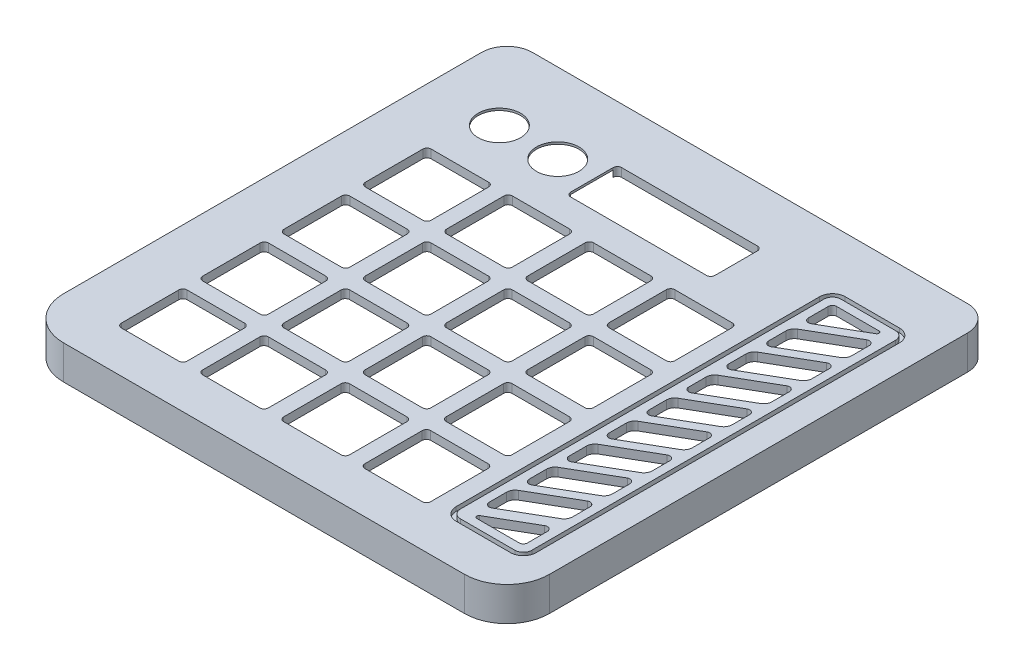
SolidWorks part; units mm, degrees
ref_plane "Plan de face" through (0, 0, 0) normal (0, 0, 1) x (1, 0, 0)
ref_plane "Plan de dessus" through (0, 0, 0) normal (0, 1, 0) x (1, 0, 0)
ref_plane "Plan de droite" through (0, 0, 0) normal (1, 0, 0) x (0, 0, -1)
sketch "Esquisse2" plane through (0, 0, 0) normal (0, 1, 0) x (1, 0, 0)
  line L1 (8, 0) -> (102.5, 0)
  line L2 (0, 8) -> (0, 106.5)
  line L3 (4, 110.5) -> (106.5, 110.5)
  line L4 (110.5, 8) -> (110.5, 106.5)
  line L5 (8, -2) -> (102.5, -2)
  line L6 (-2, 8) -> (-2, 106.5)
  line L7 (4, 112.5) -> (106.5, 112.5)
  line L8 (112.5, 8) -> (112.5, 106.5)
  arc A0 (0, 106.5) -> (4, 110.5) centre (4, 106.5) cw
  arc A1 (106.5, 110.5) -> (110.5, 106.5) centre (106.5, 106.5) cw
  arc A2 (102.5, 0) -> (110.5, 8) centre (102.5, 8) ccw
  arc A3 (8, 0) -> (0, 8) centre (8, 8) cw
  arc A4 (-2, 106.5) -> (4, 112.5) centre (4, 106.5) cw
  arc A5 (112.5, 106.5) -> (106.5, 112.5) centre (106.5, 106.5) ccw
  arc A6 (102.5, -2) -> (112.5, 8) centre (102.5, 8) ccw
  arc A7 (8, -2) -> (-2, 8) centre (8, 8) cw
  point P7 (0, 110.5)
  point P12 (110.5, 0)
  point P15 (0, 0)
  dimension "D3" = 4
  dimension "D4" = 8
  dimension "D9" = 6
  dimension "D10" = 6
  dimension "D11" = 10
  dimension "D1" = 110.5
  dimension "D2" = 110.5
  dimension "D5" = 2
  dimension "D6" = 2
  dimension "D7" = 2
  dimension "D8" = 2
extrude "Boss.-Extru.1" add sketch "Esquisse2" along normal blind 6
sketch "Esquisse3" plane through (0, 6, 0) normal (0, 1, 0) x (1, 0, 0)
  line L0 (-2, 106.5) -> (-2, 112.5) construction
  line L1 (4, 112.5) -> (-2, 112.5) construction
  line L2 (102.5, -2) -> (112.5, -2) construction
  line L3 (4, 112.5) -> (106.5, 112.5)
  line L4 (-2, 106.5) -> (-2, 8)
  line L5 (8, -2) -> (102.5, -2)
  line L6 (112.5, 106.5) -> (112.5, 8)
  line L7 (112.5, 8) -> (112.5, -2) construction
  arc A0 (106.5, 112.5) -> (112.5, 106.5) centre (106.5, 106.5) cw
  arc A1 (4, 112.5) -> (-2, 106.5) centre (4, 106.5) ccw
  arc A2 (102.5, -2) -> (112.5, 8) centre (102.5, 8) ccw
  arc A3 (-2, 8) -> (8, -2) centre (8, 8) ccw
  dimension "D1" = 6
  dimension "D2" = 10
extrude "Boss.-Extru.2" add sketch "Esquisse3" along normal blind 2
sketch "Esquisse5" plane through (0, 8, 0) normal (0, 1, 0) x (1, 0, 0)
  line L0 (112.5, 8) -> (112.5, 106.5) construction
  line L5 (-2, 106.5) -> (-2, 8) construction
  line L6 (38, 87.5) -> (70, 87.5)
  line L8 (11.8, 80.849) -> (25.3, 80.849)
  line L9 (10.8, 79.849) -> (10.8, 66.349)
  line L10 (11.8, 65.349) -> (25.3, 65.349)
  line L11 (26.3, 79.849) -> (26.3, 66.349)
  line L75 (29.9262, 79.849) -> (29.9262, 66.349)
  line L76 (30.9262, 80.849) -> (44.4262, 80.849)
  line L77 (45.4262, 79.849) -> (45.4262, 66.349)
  line L78 (30.9262, 65.349) -> (44.4262, 65.349)
  line L79 (49.0524, 79.849) -> (49.0524, 66.349)
  line L80 (50.0524, 80.849) -> (63.5524, 80.849)
  line L81 (64.5524, 79.849) -> (64.5524, 66.349)
  line L82 (50.0524, 65.349) -> (63.5524, 65.349)
  line L83 (68.1786, 79.849) -> (68.1786, 66.349)
  line L84 (69.1786, 80.849) -> (82.6786, 80.849)
  line L85 (83.6786, 79.849) -> (83.6786, 66.349)
  line L86 (69.1786, 65.349) -> (82.6786, 65.349)
  line L87 (29.9262, 60.6815) -> (29.9262, 47.1815)
  line L88 (30.9262, 61.6815) -> (44.4262, 61.6815)
  line L89 (45.4262, 60.6815) -> (45.4262, 47.1815)
  line L90 (30.9262, 46.1815) -> (44.4262, 46.1815)
  line L91 (49.0524, 60.6815) -> (49.0524, 47.1815)
  line L92 (50.0524, 61.6815) -> (63.5524, 61.6815)
  line L93 (64.5524, 60.6815) -> (64.5524, 47.1815)
  line L94 (50.0524, 46.1815) -> (63.5524, 46.1815)
  line L95 (68.1786, 60.6815) -> (68.1786, 47.1815)
  line L96 (69.1786, 61.6815) -> (82.6786, 61.6815)
  line L97 (83.6786, 60.6815) -> (83.6786, 47.1815)
  line L98 (69.1786, 46.1815) -> (82.6786, 46.1815)
  line L99 (29.9262, 41.514) -> (29.9262, 28.014)
  line L100 (30.9262, 42.514) -> (44.4262, 42.514)
  line L101 (45.4262, 41.514) -> (45.4262, 28.014)
  line L102 (30.9262, 27.014) -> (44.4262, 27.014)
  line L103 (49.0524, 41.514) -> (49.0524, 28.014)
  line L104 (50.0524, 42.514) -> (63.5524, 42.514)
  line L105 (64.5524, 41.514) -> (64.5524, 28.014)
  line L106 (50.0524, 27.014) -> (63.5524, 27.014)
  line L107 (68.1786, 41.514) -> (68.1786, 28.014)
  line L108 (69.1786, 42.514) -> (82.6786, 42.514)
  line L109 (83.6786, 41.514) -> (83.6786, 28.014)
  line L110 (69.1786, 27.014) -> (82.6786, 27.014)
  line L111 (29.9262, 22.3465) -> (29.9262, 8.8465)
  line L112 (30.9262, 23.3465) -> (44.4262, 23.3465)
  line L113 (45.4262, 22.3465) -> (45.4262, 8.8465)
  line L114 (30.9262, 7.8465) -> (44.4262, 7.8465)
  line L115 (49.0524, 22.3465) -> (49.0524, 8.8465)
  line L116 (50.0524, 23.3465) -> (63.5524, 23.3465)
  line L117 (64.5524, 22.3465) -> (64.5524, 8.8465)
  line L118 (50.0524, 7.8465) -> (63.5524, 7.8465)
  line L119 (68.1786, 22.3465) -> (68.1786, 8.8465)
  line L120 (69.1786, 23.3465) -> (82.6786, 23.3465)
  line L121 (83.6786, 22.3465) -> (83.6786, 8.8465)
  line L122 (69.1786, 7.8465) -> (82.6786, 7.8465)
  line L123 (10.8, 60.6815) -> (10.8, 47.1815)
  line L124 (11.8, 61.6815) -> (25.3, 61.6815)
  line L125 (26.3, 60.6815) -> (26.3, 47.1815)
  line L126 (11.8, 46.1815) -> (25.3, 46.1815)
  line L127 (10.8, 41.514) -> (10.8, 28.014)
  line L128 (11.8, 42.514) -> (25.3, 42.514)
  line L129 (26.3, 41.514) -> (26.3, 28.014)
  line L130 (11.8, 27.014) -> (25.3, 27.014)
  line L131 (10.8, 22.3465) -> (10.8, 8.8465)
  line L132 (11.8, 23.3465) -> (25.3, 23.3465)
  line L133 (26.3, 22.3465) -> (26.3, 8.8465)
  line L134 (11.8, 7.8465) -> (25.3, 7.8465)
  line L135 (106.5, 112.5) -> (4, 112.5) construction
  line L136 (37, 88.5) -> (37, 98.5)
  line L137 (38, 99.5) -> (70, 99.5)
  line L138 (71, 88.5) -> (71, 98.5)
  arc A0 (25.3, 65.349) -> (26.3, 66.349) centre (25.3, 66.349) ccw
  arc A1 (10.8, 66.349) -> (11.8, 65.349) centre (11.8, 66.349) ccw
  arc A2 (11.8, 80.849) -> (10.8, 79.849) centre (11.8, 79.849) ccw
  arc A3 (25.3, 80.849) -> (26.3, 79.849) centre (25.3, 79.849) cw
  arc A4 (30.9262, 80.849) -> (29.9262, 79.849) centre (30.9262, 79.849) ccw
  arc A5 (29.9262, 66.349) -> (30.9262, 65.349) centre (30.9262, 66.349) ccw
  arc A6 (44.4262, 80.849) -> (45.4262, 79.849) centre (44.4262, 79.849) cw
  arc A7 (44.4262, 65.349) -> (45.4262, 66.349) centre (44.4262, 66.349) ccw
  arc A8 (50.0524, 80.849) -> (49.0524, 79.849) centre (50.0524, 79.849) ccw
  arc A9 (49.0524, 66.349) -> (50.0524, 65.349) centre (50.0524, 66.349) ccw
  arc A10 (63.5524, 80.849) -> (64.5524, 79.849) centre (63.5524, 79.849) cw
  arc A11 (63.5524, 65.349) -> (64.5524, 66.349) centre (63.5524, 66.349) ccw
  arc A12 (69.1786, 80.849) -> (68.1786, 79.849) centre (69.1786, 79.849) ccw
  arc A13 (68.1786, 66.349) -> (69.1786, 65.349) centre (69.1786, 66.349) ccw
  arc A14 (82.6786, 80.849) -> (83.6786, 79.849) centre (82.6786, 79.849) cw
  arc A15 (82.6786, 65.349) -> (83.6786, 66.349) centre (82.6786, 66.349) ccw
  arc A16 (30.9262, 61.6815) -> (29.9262, 60.6815) centre (30.9262, 60.6815) ccw
  arc A17 (29.9262, 47.1815) -> (30.9262, 46.1815) centre (30.9262, 47.1815) ccw
  arc A18 (44.4262, 61.6815) -> (45.4262, 60.6815) centre (44.4262, 60.6815) cw
  arc A19 (44.4262, 46.1815) -> (45.4262, 47.1815) centre (44.4262, 47.1815) ccw
  arc A20 (50.0524, 61.6815) -> (49.0524, 60.6815) centre (50.0524, 60.6815) ccw
  arc A21 (49.0524, 47.1815) -> (50.0524, 46.1815) centre (50.0524, 47.1815) ccw
  arc A22 (63.5524, 61.6815) -> (64.5524, 60.6815) centre (63.5524, 60.6815) cw
  arc A23 (63.5524, 46.1815) -> (64.5524, 47.1815) centre (63.5524, 47.1815) ccw
  arc A24 (69.1786, 61.6815) -> (68.1786, 60.6815) centre (69.1786, 60.6815) ccw
  arc A25 (68.1786, 47.1815) -> (69.1786, 46.1815) centre (69.1786, 47.1815) ccw
  arc A26 (82.6786, 61.6815) -> (83.6786, 60.6815) centre (82.6786, 60.6815) cw
  arc A27 (82.6786, 46.1815) -> (83.6786, 47.1815) centre (82.6786, 47.1815) ccw
  arc A28 (30.9262, 42.514) -> (29.9262, 41.514) centre (30.9262, 41.514) ccw
  arc A29 (29.9262, 28.014) -> (30.9262, 27.014) centre (30.9262, 28.014) ccw
  arc A30 (44.4262, 42.514) -> (45.4262, 41.514) centre (44.4262, 41.514) cw
  arc A31 (44.4262, 27.014) -> (45.4262, 28.014) centre (44.4262, 28.014) ccw
  arc A32 (50.0524, 42.514) -> (49.0524, 41.514) centre (50.0524, 41.514) ccw
  arc A33 (49.0524, 28.014) -> (50.0524, 27.014) centre (50.0524, 28.014) ccw
  arc A34 (63.5524, 42.514) -> (64.5524, 41.514) centre (63.5524, 41.514) cw
  arc A35 (63.5524, 27.014) -> (64.5524, 28.014) centre (63.5524, 28.014) ccw
  arc A36 (69.1786, 42.514) -> (68.1786, 41.514) centre (69.1786, 41.514) ccw
  arc A37 (68.1786, 28.014) -> (69.1786, 27.014) centre (69.1786, 28.014) ccw
  arc A38 (82.6786, 42.514) -> (83.6786, 41.514) centre (82.6786, 41.514) cw
  arc A39 (82.6786, 27.014) -> (83.6786, 28.014) centre (82.6786, 28.014) ccw
  arc A40 (30.9262, 23.3465) -> (29.9262, 22.3465) centre (30.9262, 22.3465) ccw
  arc A41 (29.9262, 8.8465) -> (30.9262, 7.8465) centre (30.9262, 8.8465) ccw
  arc A42 (44.4262, 23.3465) -> (45.4262, 22.3465) centre (44.4262, 22.3465) cw
  arc A43 (44.4262, 7.8465) -> (45.4262, 8.8465) centre (44.4262, 8.8465) ccw
  arc A44 (50.0524, 23.3465) -> (49.0524, 22.3465) centre (50.0524, 22.3465) ccw
  arc A45 (49.0524, 8.8465) -> (50.0524, 7.8465) centre (50.0524, 8.8465) ccw
  arc A46 (63.5524, 23.3465) -> (64.5524, 22.3465) centre (63.5524, 22.3465) cw
  arc A47 (63.5524, 7.8465) -> (64.5524, 8.8465) centre (63.5524, 8.8465) ccw
  arc A48 (69.1786, 23.3465) -> (68.1786, 22.3465) centre (69.1786, 22.3465) ccw
  arc A49 (68.1786, 8.8465) -> (69.1786, 7.8465) centre (69.1786, 8.8465) ccw
  arc A50 (82.6786, 23.3465) -> (83.6786, 22.3465) centre (82.6786, 22.3465) cw
  arc A51 (82.6786, 7.8465) -> (83.6786, 8.8465) centre (82.6786, 8.8465) ccw
  arc A52 (11.8, 61.6815) -> (10.8, 60.6815) centre (11.8, 60.6815) ccw
  arc A53 (10.8, 47.1815) -> (11.8, 46.1815) centre (11.8, 47.1815) ccw
  arc A54 (25.3, 61.6815) -> (26.3, 60.6815) centre (25.3, 60.6815) cw
  arc A55 (25.3, 46.1815) -> (26.3, 47.1815) centre (25.3, 47.1815) ccw
  arc A56 (11.8, 42.514) -> (10.8, 41.514) centre (11.8, 41.514) ccw
  arc A57 (10.8, 28.014) -> (11.8, 27.014) centre (11.8, 28.014) ccw
  arc A58 (25.3, 42.514) -> (26.3, 41.514) centre (25.3, 41.514) cw
  arc A59 (25.3, 27.014) -> (26.3, 28.014) centre (25.3, 28.014) ccw
  arc A60 (11.8, 23.3465) -> (10.8, 22.3465) centre (11.8, 22.3465) ccw
  arc A61 (10.8, 8.8465) -> (11.8, 7.8465) centre (11.8, 8.8465) ccw
  arc A62 (25.3, 23.3465) -> (26.3, 22.3465) centre (25.3, 22.3465) cw
  arc A63 (25.3, 7.8465) -> (26.3, 8.8465) centre (25.3, 8.8465) ccw
  arc A66 (38, 87.5) -> (37, 88.5) centre (38, 88.5) cw
  arc A67 (70, 87.5) -> (71, 88.5) centre (70, 88.5) ccw
  arc A68 (70, 99.5) -> (71, 98.5) centre (70, 98.5) cw
  arc A69 (37, 98.5) -> (38, 99.5) centre (38, 98.5) cw
  circle A70 centre (28.75, 93.7) radius 5
  circle A71 centre (15, 93.7) radius 5
  point P82 (10.8, 65.349)
  point P85 (10.8, 80.849)
  point P88 (26.3, 80.849)
  dimension "D10" = 1
  dimension "D11" = 18.8
  dimension "D12" = 18.8
  dimension "D17" = 1
  dimension "D15" = 10
  dimension "D16" = 10
  dimension "D2" = 3.6262
  dimension "D3" = 3.6675
  dimension "D4" = 31.651
  dimension "D5" = 12.8
  dimension "D6" = 15.5
  dimension "D7" = 15.5
  dimension "D8" = 4
  dimension "D13" = 17
  dimension "D14" = 13.75
  dimension "D18" = 13
  dimension "D19" = 41.5
  dimension "D20" = 34
  dimension "D21" = 12
  dimension "D9" = 4
extrude "Enlèv. mat.-Extru.1" cut sketch "Esquisse5" against normal blind 33 contours A3 L8 A2 L9 A1 L10 A0 L11 | L78 A7 L77 A6 L76 A4 L75 A5 | L82 A11 L81 A10 L80 A8 L79 A9 | L86 A15 L85 A14 L84 A12 L83 A13 | L98 A27 L97 A26 L96 A24 L95 A25 | L94 A23 L93 A22 L92 A20 L91 A21 | L90 A19 L89 A18 L88 A16 L87 A17 | L126 A55 L125 A54 L124 A52 L123 A53 | L130 A59 L129 A58 L128 A56 L127 A57 | L102 A31 L101 A30 L100 A28 L99 A29 | L106 A35 L105 A34 L104 A32 L103 A33 | L110 A39 L109 A38 L108 A36 L107 A37 | L122 A51 L121 A50 L120 A48 L119 A49 | L118 A47 L117 A46 L116 A44 L115 A45 | L114 A43 L113 A42 L112 A40 L111 A41 | L134 A63 L133 A62 L132 A60 L131 A61 | A69 L137 A68 L138 A67 L6 A66 L136 | A71 | A70 region at (18.55, 8, -73.099) region at (37.6762, 8, -73.099) region at (56.8024, 8, -73.099) region at (75.9286, 8, -73.099) region at (37.6762, 8, -53.9315) region at (56.8024, 8, -53.9315) region at (75.9286, 8, -53.9315) region at (37.6762, 8, -34.764) region at (56.8024, 8, -34.764) region at (75.9286, 8, -34.764) region at (37.6762, 8, -15.5965) region at (56.8024, 8, -15.5965) region at (75.9286, 8, -15.5965) region at (18.55, 8, -53.9315) region at (18.55, 8, -34.764) region at (18.55, 8, -15.5965)
sketch "Esquisse6" plane through (0, 8, 0) normal (0, 1, 0) x (1, 0, 0)
  line L0 (83.6786, 79.849) -> (83.6786, 66.349) construction
  line L1 (90.6786, 99.5) -> (103.5, 99.5)
  line L2 (87.6786, 96.5) -> (87.6786, 10.8465)
  line L3 (90.6786, 7.8465) -> (103.5, 7.8465)
  line L4 (106.5, 96.5) -> (106.5, 10.8465)
  line L5 (112.5, 8) -> (112.5, 106.5) construction
  line L6 (91.6786, 87.2749) -> (102, 93.234)
  line L7 (103.5, 92.3679) -> (103.5, 88.2547)
  line L8 (102.5, 86.5226) -> (92.1786, 80.5636)
  line L9 (69.1786, 7.8465) -> (82.6786, 7.8465) construction
  line L10 (38, 99.5) -> (70, 99.5) construction
  line L11 (90.6786, 95.5) -> (90.6786, 90.8296)
  line L12 (92.1786, 89.9636) -> (101.884, 95.567)
  line L13 (101.634, 96.5) -> (91.6786, 96.5)
  line L14 (102.5, 10.8465) -> (92.5446, 10.8465)
  line L15 (92.2946, 11.7795) -> (102, 17.3829)
  line L16 (103.5, 16.5169) -> (103.5, 11.8465)
  line L17 (90.6786, 96.5) -> (90.6786, 10.8465) construction
  line L18 (103.5, 10.8465) -> (103.5, 96.5) construction
  line L19 (90.6786, 81.4296) -> (90.6786, 85.5429)
  line L20 (90.6786, 72.0296) -> (90.6786, 76.1429)
  line L21 (91.6786, 77.8749) -> (102, 83.834)
  line L22 (103.5, 82.9679) -> (103.5, 78.8547)
  line L23 (102.5, 77.1226) -> (92.1786, 71.1636)
  line L24 (90.6786, 62.6296) -> (90.6786, 66.7429)
  line L25 (91.6786, 68.4749) -> (102, 74.434)
  line L26 (103.5, 73.5679) -> (103.5, 69.4547)
  line L27 (102.5, 67.7226) -> (92.1786, 61.7636)
  line L28 (90.6786, 53.2296) -> (90.6786, 57.3429)
  line L29 (91.6786, 59.0749) -> (102, 65.034)
  line L30 (103.5, 64.1679) -> (103.5, 60.0547)
  line L31 (102.5, 58.3226) -> (92.1786, 52.3636)
  line L32 (90.6786, 43.8296) -> (90.6786, 47.9429)
  line L33 (91.6786, 49.6749) -> (102, 55.634)
  line L34 (103.5, 54.7679) -> (103.5, 50.6547)
  line L35 (102.5, 48.9226) -> (92.1786, 42.9636)
  line L36 (90.6786, 34.4296) -> (90.6786, 38.5429)
  line L37 (91.6786, 40.2749) -> (102, 46.234)
  line L38 (103.5, 45.3679) -> (103.5, 41.2547)
  line L39 (102.5, 39.5226) -> (92.1786, 33.5636)
  line L40 (90.6786, 25.0296) -> (90.6786, 29.1429)
  line L41 (91.6786, 30.8749) -> (102, 36.834)
  line L42 (103.5, 35.9679) -> (103.5, 31.8547)
  line L43 (102.5, 30.1226) -> (92.1786, 24.1636)
  line L44 (90.6786, 15.6296) -> (90.6786, 19.7429)
  line L45 (91.6786, 21.4749) -> (102, 27.434)
  line L46 (103.5, 26.5679) -> (103.5, 22.4547)
  line L47 (102.5, 20.7226) -> (92.1786, 14.7636)
  line L48 (88.6786, 96.5) -> (88.6786, 10.8465)
  line L49 (90.6786, 8.8465) -> (103.5, 8.8465)
  line L50 (105.5, 96.5) -> (105.5, 10.8465)
  line L51 (90.6786, 98.5) -> (103.5, 98.5)
  arc A0 (103.5, 7.8465) -> (106.5, 10.8465) centre (103.5, 10.8465) ccw
  arc A1 (87.6786, 10.8465) -> (90.6786, 7.8465) centre (90.6786, 10.8465) ccw
  arc A2 (103.5, 99.5) -> (106.5, 96.5) centre (103.5, 96.5) cw
  arc A3 (90.6786, 99.5) -> (87.6786, 96.5) centre (90.6786, 96.5) ccw
  arc A4 (102, 27.434) -> (103.5, 26.5679) centre (102.5, 26.5679) cw
  arc A5 (90.6786, 15.6296) -> (92.1786, 14.7636) centre (91.6786, 15.6296) ccw
  arc A6 (90.6786, 25.0296) -> (92.1786, 24.1636) centre (91.6786, 25.0296) ccw
  arc A7 (102, 36.834) -> (103.5, 35.9679) centre (102.5, 35.9679) cw
  arc A8 (90.6786, 34.4296) -> (92.1786, 33.5636) centre (91.6786, 34.4296) ccw
  arc A9 (102, 46.234) -> (103.5, 45.3679) centre (102.5, 45.3679) cw
  arc A10 (102, 55.634) -> (103.5, 54.7679) centre (102.5, 54.7679) cw
  arc A11 (90.6786, 43.8296) -> (92.1786, 42.9636) centre (91.6786, 43.8296) ccw
  arc A12 (90.6786, 53.2296) -> (92.1786, 52.3636) centre (91.6786, 53.2296) ccw
  arc A13 (102, 65.034) -> (103.5, 64.1679) centre (102.5, 64.1679) cw
  arc A14 (90.6786, 62.6296) -> (92.1786, 61.7636) centre (91.6786, 62.6296) ccw
  arc A15 (102, 74.434) -> (103.5, 73.5679) centre (102.5, 73.5679) cw
  arc A16 (102, 83.834) -> (103.5, 82.9679) centre (102.5, 82.9679) cw
  arc A17 (90.6786, 72.0296) -> (92.1786, 71.1636) centre (91.6786, 72.0296) ccw
  arc A18 (92.1786, 80.5636) -> (90.6786, 81.4296) centre (91.6786, 81.4296) cw
  arc A19 (102, 93.234) -> (103.5, 92.3679) centre (102.5, 92.3679) cw
  arc A20 (90.6786, 19.7429) -> (91.6786, 21.4749) centre (92.6786, 19.7429) cw
  arc A21 (103.5, 22.4547) -> (102.5, 20.7226) centre (101.5, 22.4547) cw
  arc A22 (103.5, 31.8547) -> (102.5, 30.1226) centre (101.5, 31.8547) cw
  arc A23 (90.6786, 29.1429) -> (91.6786, 30.8749) centre (92.6786, 29.1429) cw
  arc A24 (103.5, 41.2547) -> (102.5, 39.5226) centre (101.5, 41.2547) cw
  arc A25 (90.6786, 38.5429) -> (91.6786, 40.2749) centre (92.6786, 38.5429) cw
  arc A26 (103.5, 50.6547) -> (102.5, 48.9226) centre (101.5, 50.6547) cw
  arc A27 (90.6786, 47.9429) -> (91.6786, 49.6749) centre (92.6786, 47.9429) cw
  arc A28 (103.5, 60.0547) -> (102.5, 58.3226) centre (101.5, 60.0547) cw
  arc A29 (90.6786, 57.3429) -> (91.6786, 59.0749) centre (92.6786, 57.3429) cw
  arc A30 (103.5, 88.2547) -> (102.5, 86.5226) centre (101.5, 88.2547) cw
  arc A31 (91.6786, 87.2749) -> (90.6786, 85.5429) centre (92.6786, 85.5429) ccw
  arc A32 (103.5, 78.8547) -> (102.5, 77.1226) centre (101.5, 78.8547) cw
  arc A33 (90.6786, 76.1429) -> (91.6786, 77.8749) centre (92.6786, 76.1429) cw
  arc A34 (90.6786, 66.7429) -> (91.6786, 68.4749) centre (92.6786, 66.7429) cw
  arc A35 (103.5, 69.4547) -> (102.5, 67.7226) centre (101.5, 69.4547) cw
  arc A36 (101.884, 95.567) -> (101.634, 96.5) centre (101.634, 96) ccw
  arc A37 (92.5446, 10.8465) -> (92.2946, 11.7795) centre (92.5446, 11.3465) cw
  arc A38 (102.5, 10.8465) -> (103.5, 11.8465) centre (102.5, 11.8465) ccw
  arc A39 (102, 17.3829) -> (103.5, 16.5169) centre (102.5, 16.5169) cw
  arc A40 (90.6786, 90.8296) -> (92.1786, 89.9636) centre (91.6786, 90.8296) ccw
  arc A41 (90.6786, 95.5) -> (91.6786, 96.5) centre (91.6786, 95.5) cw
  arc A42 (88.6786, 10.8465) -> (90.6786, 8.8465) centre (90.6786, 10.8465) ccw
  arc A43 (103.5, 8.8465) -> (105.5, 10.8465) centre (103.5, 10.8465) ccw
  arc A44 (103.5, 98.5) -> (105.5, 96.5) centre (103.5, 96.5) cw
  arc A45 (90.6786, 98.5) -> (88.6786, 96.5) centre (90.6786, 96.5) ccw
  point P84 (90.6786, 79.6976)
  point P87 (103.5, 94.1)
  point P110 (103.5, 87.1)
  point P113 (90.6786, 86.6976)
  point P135 (90.6786, 89.0976)
  dimension "D3" = 3
  dimension "D11" = 1
  dimension "D12" = 2
  dimension "D13" = 0.5
  dimension "D14" = 1
  dimension "D1" = 4
  dimension "D2" = 6
  dimension "D4" = 30
  dimension "D5" = 30
  dimension "D6" = 2.4
  dimension "D7" = 2.4
  dimension "D8" = 7
  dimension "D9" = 8
  dimension "D10" = 2.0785
  dimension "D15" = 1
extrude "Enlèv. mat.-Extru.2" cut sketch "Esquisse6" against normal blind 2 contours L12 L13 L11 | L23 L22 L21 L20 | L27 L26 L25 L24 | L31 L30 L29 L28 | L35 L34 L33 L32 | L39 L38 L37 L36 | L43 L42 L41 L40 | L47 L46 L45 L44 | L16 L15 L14 | L19 A31 L6 A19 L7 A30 L8 A18 region at (94.9297, 8, -94.057) region at (99.2489, 8, -13.2895) region at (97.0893, 8, -77.4988) region at (97.0893, 8, -68.0988) region at (97.0893, 8, -58.6988) region at (97.0893, 8, -49.2988) region at (97.0893, 8, -39.8988) region at (97.0893, 8, -30.4988) region at (97.0893, 8, -21.0988)
extrude "Enlèv. mat.-Extru.3" cut sketch "Esquisse6<3>" against normal blind 1 contours L2 A1 L3 A0 L4 A2 L1 A3 | L48 A42 L49 A43 L50 A44 L51 A45
sketch "Esquisse6<3>" plane through (0, 8, 0) normal (0, 1, 0) x (1, 0, 0) same geometry as "Esquisse6"
sketch "Esquisse12" plane through (0, 6, 0) normal (0, -1, 0) x (1, 0, 0)
  line L0 (0, -106.5) -> (0, -8) construction
  line L1 (7, -83.7) -> (37, -83.7)
  line L2 (7, -83.7) -> (7, -103.7)
  line L3 (7, -103.7) -> (37, -103.7)
  line L4 (37, -83.7) -> (37, -103.7)
  circle A0 centre (15, -93.7) radius 5 construction
  dimension "D1" = 7
  dimension "D2" = 30
  dimension "D3" = 20
  dimension "D4" = 10
extrude "Enlèv. mat.-Extru.7" cut sketch "Esquisse12" against normal blind 1.5
sketch "Esquisse11" plane through (0, 0, -112.5) normal (0, 0, -1) x (-1, 0, 0)
  line L0 (-106.5, 0) -> (-4, 0) construction
  line L1 (-99.75, 0) -> (-83.75, 0)
  line L2 (-99.75, 0) -> (-99.75, 4)
  line L3 (-97.75, 6) -> (-85.75, 6)
  line L4 (-83.75, 0) -> (-83.75, 4)
  line L5 (-112.5, 8) -> (-112.5, 0) construction
  line L19 (-85.75, 6) -> (-83.75, 6)
  line L20 (-83.75, 6) -> (-83.75, 4)
  arc A0 (-97.75, 6) -> (-99.75, 4) centre (-97.75, 4) ccw
  dimension "D3" = 2
  dimension "D1" = 12.75
  dimension "D2" = 16
  dimension "D4" = 6
extrude "Enlèv. mat.-Extru.6" cut sketch "Esquisse11" against normal blind 10
sketch "Esquisse13" plane through (112.5, 0, 0) normal (1, 0, 0) x (0, 0, -1)
  line L0 (110.5, 6) -> (109.442, 0)
  line L1 (106.5, 0) -> (112.5, 0) construction
  line L2 (109.442, 0) -> (111.442, 0)
  line L3 (111.442, 0) -> (112.5, 6)
  line L4 (112.5, 6) -> (110.5, 6)
  line L5 (110.5, 6) -> (112.5, 6) construction
  line L6 (110.5, 6) -> (110.5, 0) construction
  dimension "D1" = 100
  dimension "D2" = 80
extrude "Boss.-Extru.3" add sketch "Esquisse13" against normal blind 79.5 from offset 28.75 contours L0 L2 L3 L4 offset against normal yes
sketch "Esquisse14" plane through (112.5, 0, 0) normal (1, 0, 0) x (0, 0, -1)
  line L0 (111.442, 0) -> (112.5, 0)
  line L1 (112.5, 0) -> (112.5, 6)
  line L2 (112.5, 6) -> (111.442, 0)
extrude "Enlèv. mat.-Extru.8" cut sketch "Esquisse14" against normal blind 79.5 from offset 28.75 offset against normal yes
sketch "Esquisse15" plane through (0, 0, -112.5) normal (0, 0, -1) x (-1, 0, 0)
  line L0 (-4.25, 6) -> (-83.75, 6) construction
  line L1 (-4.25, 0) -> (-5.25, 0)
  line L2 (-4.25, 0) -> (-4.25, 6)
  line L3 (-4.25, 6) -> (-5.25, 6)
  line L4 (-5.25, 0) -> (-5.25, 6)
  line L6 (-31.75, 6) -> (-30.75, 6)
  line L7 (-31.75, 6) -> (-31.75, 0)
  line L8 (-31.75, 0) -> (-30.75, 0)
  line L9 (-30.75, 6) -> (-30.75, 0)
  line L10 (-58.25, 6) -> (-57.25, 6)
  line L11 (-58.25, 6) -> (-58.25, 0)
  line L12 (-58.25, 0) -> (-57.25, 0)
  line L13 (-57.25, 6) -> (-57.25, 0)
  line M10 (-83.75, 6) -> (-4.25, 6)
  dimension "D1" = 1
  dimension "D2" = 1
  dimension "D3" = 1
extrude "Enlèv. mat.-Extru.9" cut sketch "Esquisse15" against normal blind 5 contours L9 L7 L8 M10 | L13 L12 L11 L10 | L4 L3 L2 L1 region at (31.25, 3, -112.5)
